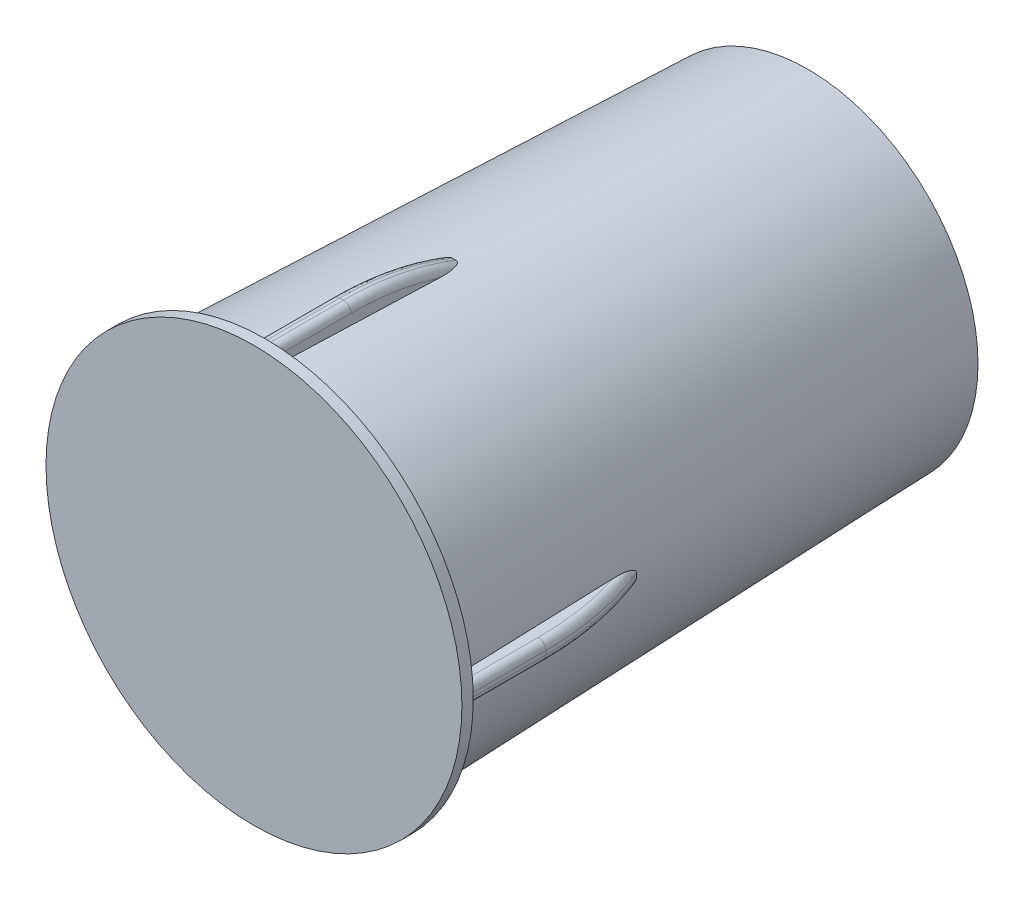
SolidWorks part; units mm, degrees
ref_plane "Plan de face" through (0, 0, 0) normal (0, 0, 1) x (1, 0, 0)
ref_plane "Plan de dessus" through (0, 0, 0) normal (0, 1, 0) x (1, 0, 0)
ref_plane "Plan de droite" through (0, 0, 0) normal (1, 0, 0) x (0, 0, -1)
sketch "Esquisse1" plane through (0, 0, 0) normal (1, 0, 0) x (0, 0, -1)
  line L0 (-9.5622, 0) -> (19.0522, 0) construction
  line L1 (0, 0) -> (0, 5.5)
  line L2 (0, 5.5) -> (0.3, 5.5)
  line L3 (0.3, 5.5) -> (0.3, 5)
  line L4 (0.3, 5) -> (14.65, 4.5)
  line L5 (14.65, 4.5) -> (14.65, 3.5)
  line L6 (14.65, 3.5) -> (9.15, 3.5)
  line L7 (9.15, 3.5) -> (9.15, 0)
  line L8 (0, 0) -> (9.15, 0)
  dimension "D1" = 14.65
  dimension "D2" = 1
  dimension "D3" = 5.5
  dimension "D4" = 0.3
  dimension "D5" = 4.5
  dimension "D6" = 5
  dimension "D7" = 0.5
revolve "Révolution1" add sketch "Esquisse1" angle 360 about L8
sketch "Esquisse3" plane through (0, 0, 0) normal (1, 0, 0) x (0, 0, -1)
  line L0 (0.3, 0.25) -> (5.3, 0.25)
  line L1 (0.3, -5) -> (0.3, 5) construction
  line L2 (5.3, 0.25) -> (5.3, -0.25)
  line L3 (5.3, -0.25) -> (0.3, -0.25)
  line L4 (0.3, 0.25) -> (0.3, -0.25)
  line L5 (-1.4247, 0) -> (17.1765, 0) construction
  dimension "D1" = 0.5
  dimension "D2" = 5
extrude "Boss.-Extru.1" add sketch "Esquisse3" along normal blind 5.4
chamfer "Chanfrein1" distance 1 angle 30 1 edges at (5.4, 0, -5.3) first distance on face at (5.4, 0, -2.8)
fillet "Congé2" radius 8 1 edges at (5.4, 0, -4.3)
fillet "Congé3" radius 0.2 4 edges at (5.4, -0.25, -1.3043) (5.4, 0.25, -1.3043)
pattern_circular "Répétition circulaire1" count 4 every 90 about axis through (0, 0, 0) along (0, 0, 1) of "Congé3", "Boss.-Extru.1", "Chanfrein1", "Congé2"
